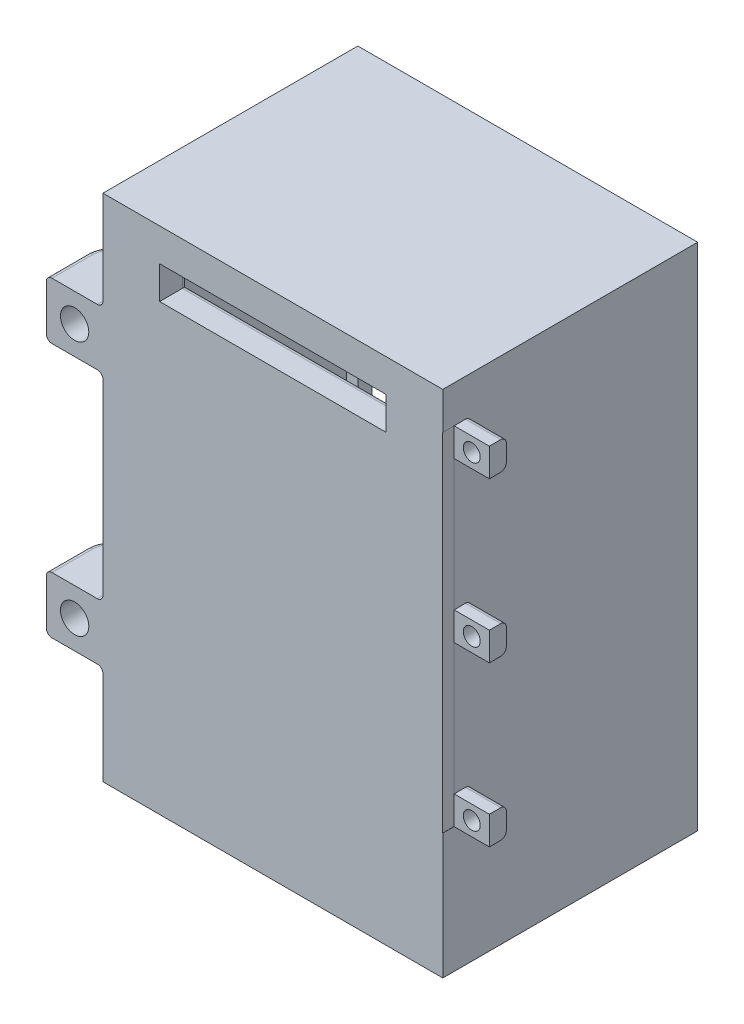
SolidWorks part; units mm, degrees
ref_plane "Plan de face" through (0, 0, 0) normal (0, 0, 1) x (1, 0, 0)
ref_plane "Plan de dessus" through (0, 0, 0) normal (0, 1, 0) x (1, 0, 0)
ref_plane "Plan de droite" through (0, 0, 0) normal (1, 0, 0) x (0, 0, -1)
sketch "Esquisse1" plane through (0, 0, 0) normal (0, 0, 1) x (1, 0, 0)
  line L0 (-42.5, 42.5) -> (0, 0)
  line L1 (-50, 50) -> (50, 50)
  line L2 (-50, 50) -> (-50, -50)
  line L3 (-50, -50) -> (50, -50)
  line L4 (50, 50) -> (50, -50)
  line L5 (-50, 50) -> (50, -50) construction
  line L6 (-50, -50) -> (50, 50) construction
  line L7 (-42.5, 42.5) -> (42.5, 42.5)
  line L8 (-42.5, 42.5) -> (-42.5, -42.5)
  line L9 (-42.5, -42.5) -> (42.5, -42.5)
  line L10 (42.5, 42.5) -> (42.5, -42.5)
  line L11 (-42.5, 42.5) -> (42.5, -42.5) construction
  line L12 (-42.5, -42.5) -> (42.5, 42.5) construction
  line L13 (0, 0) -> (42.5, -42.5)
  line L14 (-42.5, -42.5) -> (0, 0)
  line L15 (0, 0) -> (42.5, 42.5)
  line L16 (-42.5, 42.5) -> (-50, 42.5)
  line L17 (-50, 42.5) -> (-42.5, 50)
  line L18 (-42.5, 50) -> (-42.5, 42.5)
  line L19 (-46.25, 46.25) -> (-44.4822, 48.0178)
  line L20 (-46.25, 46.25) -> (-48.0178, 44.4822)
  line L21 (44.4822, -48.0178) -> (-47.9542, 44.5507)
  line L22 (44.4822, -48.0178) -> (47.9542, -44.5507)
  line L23 (-47.9542, 44.5507) -> (-44.4822, 48.0178)
  line L24 (47.9542, -44.5507) -> (-44.4822, 48.0178)
  line L25 (44.4822, -48.0178) -> (-44.4822, 48.0178) construction
  line L26 (-47.9542, 44.5507) -> (47.9542, -44.5507) construction
  line L27 (42.5, 42.5) -> (42.5, 50)
  line L28 (42.5, 42.5) -> (50, 42.5)
  line L29 (50, 42.5) -> (42.5, 50)
  line L30 (46.25, 46.25) -> (44.3148, 48.1852)
  line L31 (46.25, 46.25) -> (47.8504, 44.6496)
  line L32 (-44.3148, -48.1852) -> (48.1852, 44.3148)
  line L33 (-44.3148, -48.1852) -> (-48.1852, -44.3148)
  line L34 (48.1852, 44.3148) -> (44.3148, 48.1852)
  line L35 (-48.1852, -44.3148) -> (44.3148, 48.1852)
  line L36 (-44.3148, -48.1852) -> (44.3148, 48.1852) construction
  line L37 (48.1852, 44.3148) -> (-48.1852, -44.3148) construction
  circle A0 centre (0, 0) radius 29
  circle A1 centre (0, 0) radius 34
  point P0 (0, 0)
  point P6 (0, 0)
  dimension "D5" = 58
  dimension "D6" = 68
  dimension "D1" = 100
  dimension "D2" = 100
  dimension "D3" = 85
  dimension "D4" = 85
  dimension "D7" = 2.5
  dimension "D8" = 2.5
  dimension "D9" = 5
extrude "Boss.-Extru.2" add sketch "Esquisse1" along normal blind 10 contours L7 L35 L27 L1 L18 L24 | L33 L35 L8 L21 L16 L2 L3 L4 L28 L32 L10 L24 L22 L9 | L21 A1 L35 A0 | L32 A1 L21 A0 | L35 A1 L24 A0 | L24 A1 L32 A0 | A1 L32 L10 L15 | A1 L15 L7 L35 | L15 A1 L35 A0 | L32 A1 L15 A0 | L24 A1 L0 A0 | A1 L24 L7 L0 | L0 A1 L21 A0 | L21 A1 L13 A0 | L13 A1 L24 A0 | A1 L13 L10 L24 | A1 L21 L9 L13 | L22 L24 L10 L9 L21 | L35 L33 L32 L9 L8 | A1 L35 L8 L14 | A1 L14 L9 L32 | L35 A1 L14 A0 | L14 A1 L32 A0 | A1 L0 L8 L21 | L21 L8 L16 | L7 L24 L18 | L18 L24 L17 L20 L21 L16 | L16 L21 L17 | L21 L23 L17 L1 L2 | L24 L18 L17 | L27 L35 L29 | L35 L27 L28 L32 L29 | L32 L28 L29 | L29 L4 L1 | L10 L32 L28 | L35 L7 L27 | L16 L17 L18 region at (-31.9722, 33.7018, 0) region at (-41.3241, 43.6776, 0) region at (-33.6728, 31.9878, 0) region at (-43.6355, 41.3629, 0) region at (-44.7427, 44.7878, 0) region at (-21.3754, 23.1269, 0) region at (-23.111, 21.3913, 0) region at (-0.082, 46.3052, 0) region at (-43.8622, 0.2295, 0) region at (-47.9527, 43.1828, 0) region at (-43.1607, 48.0168, 0) region at (-0.1204, 29.0381, 0) region at (-29.033, 0.1411, 0) region at (41.2099, 43.7901, 0) region at (31.8324, 33.7334, 0) region at (-33.7334, -31.8324, 0) region at (-43.8581, -43.8581, 0) region at (-47.5002, 47.5005, 0) region at (21.2774, 23.2138, 0) region at (-23.2138, -21.2774, 0) region at (43.7901, 41.2099, 0) region at (33.7334, 31.8324, 0) region at (44.8027, 44.8027, 0) region at (43.1049, 48.1852, 0) region at (-31.8324, -33.7334, 0) region at (47.5, 47.5, 0) region at (23.2138, 21.2774, 0) region at (-21.2774, -23.2138, 0) region at (48.1852, 43.1049, 0) region at (29.033, -0.1411, 0) region at (0.1204, -29.0381, 0) region at (43.8779, -43.9513, 0) region at (33.6728, -31.9878, 0) region at (31.9722, -33.7018, 0) region at (23.111, -21.3913, 0) region at (21.3754, -23.1269, 0)
sketch "Esquisse2" plane through (0, 50, 0) normal (0, 1, 0) x (-1, 0, 0)
  line L0 (50, 5) -> (-50, 5)
  line L1 (50, 10) -> (50, 0) construction
  line L2 (-50, 10) -> (-50, 0) construction
  line L4 (2.5, 7.5) -> (-2.5, 7.5)
  line L5 (2.5, 7.5) -> (2.5, 2.5)
  line L6 (2.5, 2.5) -> (-2.5, 2.5)
  line L7 (-2.5, 7.5) -> (-2.5, 2.5)
  line L8 (2.5, 7.5) -> (-2.5, 2.5) construction
  line L9 (2.5, 2.5) -> (-2.5, 7.5) construction
  point P6 (0, 5)
  dimension "D1" = 5
  dimension "D2" = 5
extrude "Boss.-Extru.3" add sketch "Esquisse2" along normal blind 5 contours L0 L7 L6 L5 | L4 L7 L0 L5 region at (0, 50, 3.75) region at (0, 50, 6.25)
sketch "Esquisse3" plane through (0, 55, 0) normal (0, 1, 0) x (-1, 0, 0)
  line L0 (2.5, 5) -> (-2.5, 5)
  line L1 (2.5, 7.5) -> (2.5, 2.5) construction
  line L2 (-2.5, 7.5) -> (-2.5, 2.5) construction
  line L3 (2.5, 5) -> (2.5, 4)
  line L4 (2.5, 4) -> (-2.5, 4)
  line L5 (-2.5, 4) -> (-2.5, 5)
  line L6 (2.5, 5) -> (2.5, 6)
  line L7 (2.5, 6) -> (-2.5, 6)
  line L8 (-2.5, 6) -> (-2.5, 5)
  line M1 (2.5, 2.5) -> (2.5, 7.5)
  line M3 (-2.5, 7.5) -> (-2.5, 2.5)
  dimension "D1" = 1
  dimension "D2" = 1
extrude "Enlèv. mat.-Extru.1" cut sketch "Esquisse3" against normal blind 2 contours L4 L0 M1 M3 | L7 L0 M1 M3 region at (0, 55, 4.5) region at (0, 55, 5.5)
sketch "Esquisse4" plane through (-2.5, 0, 0) normal (-1, 0, 0) x (0, 0, 1)
  line L0 (6, 53) -> (6, 68)
  line L1 (6, 53) -> (4, 53)
  line L2 (4, 53) -> (4, 68)
  line L3 (4, 68) -> (6, 68)
  dimension "D1" = 15
extrude "Boss.-Extru.4" add sketch "Esquisse4" along normal blind 50 and the other way blind 55
sketch "Esquisse5" plane through (0, 0, 6) normal (0, 0, 1) x (1, 0, 0)
  line L0 (52.5, 60.5) -> (12.5, 60.5)
  line L1 (52.5, 53) -> (52.5, 68) construction
  line L2 (-52.5, 60.5) -> (-12.5, 60.5)
  line L3 (52.5, 58.5) -> (12.5, 58.5)
  line L4 (52.5, 58.5) -> (52.5, 62.5)
  line L5 (52.5, 62.5) -> (12.5, 62.5)
  line L6 (12.5, 58.5) -> (12.5, 62.5)
  line L7 (52.5, 58.5) -> (12.5, 62.5) construction
  line L8 (52.5, 62.5) -> (12.5, 58.5) construction
  line L9 (-52.5, 53) -> (-52.5, 68) construction
  line L11 (-52.5, 58.5) -> (-12.5, 58.5)
  line L12 (-52.5, 58.5) -> (-52.5, 62.5)
  line L13 (-52.5, 62.5) -> (-12.5, 62.5)
  line L14 (-12.5, 58.5) -> (-12.5, 62.5)
  line L15 (-52.5, 58.5) -> (-12.5, 62.5) construction
  line L16 (-52.5, 62.5) -> (-12.5, 58.5) construction
  point P4 (32.5, 60.5)
  point P13 (-32.5, 60.5)
  point P14 (-32.5, 60.5)
  line M8 (-52.5, 68) -> (-52.5, 53)
  dimension "D1" = 4
  dimension "D2" = 40
  dimension "D3" = 40
  dimension "D4" = 4
extrude "Enlèv. mat.-Extru.2" cut sketch "Esquisse5" against normal blind 1 contours L2 L14 L13 M8 | L11 L14 L2 M8 | L6 L0 L4 L5 | L6 L3 L4 L0 region at (32.5, 59.5, 6) region at (32.5, 61.5, 6) region at (-32.5, 61.5, 6) region at (-32.5, 59.5, 6)
sketch "Esquisse6" plane through (0, 0, 6) normal (0, 0, 1) x (1, 0, 0)
  line L0 (-52.5, 58.5) -> (-12.5, 58.5) construction
  line L1 (-12.5, 58.5) -> (-32.5, 58.5) construction
  line L2 (-32.5, 58.5) -> (-32.5, 62.5) construction
  line L3 (-52.5, 62.5) -> (-12.5, 62.5) construction
  line L4 (-32.5, 58.5) -> (-12.5, 58.5) construction
  line L5 (-12.5, 58.5) -> (-22.5, 58.5) construction
  line L6 (-22.5, 58.5) -> (-22.5, 62.5) construction
  line L7 (-52.5, 58.5) -> (-32.5, 58.5) construction
  line L8 (-42.5, 58.5) -> (-42.5, 62.5) construction
  line L9 (12.5, 58.5) -> (52.5, 58.5) construction
  line L10 (52.5, 58.5) -> (32.5, 58.5) construction
  line L11 (32.5, 58.5) -> (32.5, 62.5) construction
  line L12 (52.5, 62.5) -> (12.5, 62.5) construction
  line L13 (32.5, 58.5) -> (52.5, 58.5) construction
  line L14 (42.5, 58.5) -> (42.5, 62.5) construction
  line L15 (32.5, 58.5) -> (12.5, 58.5) construction
  line L16 (22.5, 58.5) -> (22.5, 62.5) construction
  line L18 (-44, 56.5) -> (-41, 56.5)
  line L19 (-44, 56.5) -> (-44, 64.5)
  line L20 (-44, 64.5) -> (-41, 64.5)
  line L21 (-41, 56.5) -> (-41, 64.5)
  line L22 (-44, 56.5) -> (-41, 64.5) construction
  line L23 (-44, 64.5) -> (-41, 56.5) construction
  line L24 (-24, 56.5) -> (-21, 56.5)
  line L25 (-24, 56.5) -> (-24, 64.5)
  line L26 (-24, 64.5) -> (-21, 64.5)
  line L27 (-21, 56.5) -> (-21, 64.5)
  line L28 (-24, 56.5) -> (-21, 64.5) construction
  line L29 (-24, 64.5) -> (-21, 56.5) construction
  line L30 (21, 56.5) -> (24, 56.5)
  line L31 (21, 56.5) -> (21, 64.5)
  line L32 (21, 64.5) -> (24, 64.5)
  line L33 (24, 56.5) -> (24, 64.5)
  line L34 (21, 56.5) -> (24, 64.5) construction
  line L35 (21, 64.5) -> (24, 56.5) construction
  line L36 (41, 56.5) -> (44, 56.5)
  line L37 (41, 56.5) -> (41, 64.5)
  line L38 (41, 64.5) -> (44, 64.5)
  line L39 (44, 56.5) -> (44, 64.5)
  line L40 (41, 56.5) -> (44, 64.5) construction
  line L41 (41, 64.5) -> (44, 56.5) construction
  point P24 (-42.5, 60.5)
  point P29 (-22.5, 60.5)
  point P34 (22.5, 60.5)
  point P39 (42.5, 60.5)
  dimension "D1" = 8
  dimension "D2" = 3
  dimension "D3" = 8
  dimension "D4" = 3
  dimension "D5" = 8
  dimension "D6" = 3
  dimension "D7" = 3
  dimension "D8" = 8
extrude "Boss.-Extru.5" add sketch "Esquisse6" along normal blind 2
sketch "Esquisse7" plane through (0, 0, 0) normal (0, 0, -1) x (-1, 0, 0)
  line L0 (-50, 50) -> (50, -50) construction
  line L1 (50, 50) -> (-50, -50) construction
  line L2 (-42.5, -39.0887) -> (-42.5, -42.5) construction
  line L3 (-42.5, -42.5) -> (-38.9723, -42.5) construction
  line L4 (-50, -50) -> (-42.5, -42.5) construction
  line L5 (-42.5, -42.5) -> (-50, -50) construction
  line L6 (-50, -50) -> (-46.25, -46.25) construction
  line L7 (-46.25, -46.25) -> (-46.25, 46.25) construction
  line L8 (-46.25, 46.25) -> (46.217, 46.283) construction
  line L9 (47.9517, 44.5483) -> (44.4822, 48.0178) construction
  line L10 (46.217, 46.283) -> (46.217, -46.217) construction
  line L11 (46.217, -46.217) -> (-46.25, -46.25) construction
  circle A0 centre (-46.25, 46.25) radius 2.5
  circle A1 centre (46.217, 46.283) radius 2.5
  circle A2 centre (46.217, -46.217) radius 2.5
  circle A3 centre (-46.25, -46.25) radius 2.5
  dimension "D1" = 5
  dimension "D2" = 5
  dimension "D3" = 5
  dimension "D4" = 5
extrude "Enlèv. mat.-Extru.3" cut sketch "Esquisse7" against normal blind 10
fillet "Congé1" radius 5 2 edges at (0, 55, 7.5) (0, 55, 2.5)
fillet "Congé4" radius 1 6 edges at (-27.5, 53, 6) (27.5, 53, 6) (27.5, 53, 4) (-27.5, 53, 4) (0, 68, 6) (0, 68, 4)
fillet "Congé5" radius 1 8 edges at (50, 0, 10) (0, -50, 10) (-50, 0, 10) (0, 50, 10) (0, -50, 0) (-50, 0, 0) (0, 50, 0) (50, 0, 0)
fillet "Congé6" radius 1 28 edges at (-49.7071, -49.7071, 9.7071) (-49.7071, -49.7071, 0.2929) (49.7071, -49.7071, 9.7071) (49.7071, -49.7071, 0.2929) (-49.7071, 49.7071, 9.7071) (-49.7071, 49.7071, 0.2929) (49.7071, 49.7071, 9.7071) (49.7071, 49.7071, 0.2929) (-42.5, 0.2295, 0) (-34.1994, -30.3291, 0) (-30.3291, -34.1994, 0) (0.1713, -42.5, 0) (30.5991, -34.1148, 0) (34.0989, -30.6756, 0) (42.5, -0.2295, 0) (34.1994, 30.3291, 0) (30.3291, 34.1994, 0) (-0.1713, 42.5, 0) (-30.5991, 34.1148, 0) (-34.0989, 30.6756, 0) (-33.9997, 0.1543, 0) (-0.13, 33.9998, 0) (33.9997, -0.1543, 0) (0.13, -33.9998, 0) (-50, -50, 5) (50, -50, 5) (-50, 50, 5) (50, 50, 5)
fillet "Congé7" radius 2 8 edges at (42.5, 56.5, 8) (42.5, 64.5, 8) (22.5, 56.5, 8) (22.5, 64.5, 8) (-22.5, 56.5, 8) (-22.5, 64.5, 8) (-42.5, 56.5, 8) (-42.5, 64.5, 8)
sketch "Esquisse8" plane through (0, 50, 0) normal (0, 1, 0) x (-1, 0, 0)
  line L0 (49, 5) -> (-49, 5) construction
  line L1 (49, 1) -> (49, 9) construction
  line L2 (-49, 9) -> (-49, 1) construction
  line L3 (-49, 5) -> (0, 5) construction
  line L4 (0, 5) -> (-24.5, 5) construction
  line L5 (-24.5, 5) -> (-49, 5) construction
  line L6 (-49, 5) -> (-36.75, 5) construction
  line L7 (-36.75, 5) -> (-36.75, 9) construction
  line L8 (49, 9) -> (-49, 9) construction
  line L9 (-36.75, 9) -> (-36.75, 1) construction
  line L10 (-49, 1) -> (49, 1) construction
  line L11 (49, 5) -> (0, 5) construction
  line L12 (0, 5) -> (24.5, 5) construction
  line L13 (24.5, 5) -> (49, 5) construction
  line L14 (49, 5) -> (36.75, 5) construction
  line L15 (36.75, 1) -> (36.75, 9) construction
  line L17 (39.25, 2.5) -> (34.25, 2.5)
  line L18 (39.25, 2.5) -> (39.25, 7.5)
  line L19 (39.25, 7.5) -> (34.25, 7.5)
  line L20 (34.25, 2.5) -> (34.25, 7.5)
  line L21 (39.25, 2.5) -> (34.25, 7.5) construction
  line L22 (39.25, 7.5) -> (34.25, 2.5) construction
  line L23 (-34.25, 2.5) -> (-39.25, 2.5)
  line L24 (-34.25, 2.5) -> (-34.25, 7.5)
  line L25 (-34.25, 7.5) -> (-39.25, 7.5)
  line L26 (-39.25, 2.5) -> (-39.25, 7.5)
  line L27 (-34.25, 2.5) -> (-39.25, 7.5) construction
  line L28 (-34.25, 7.5) -> (-39.25, 2.5) construction
  dimension "D1" = 5
  dimension "D2" = 5
  dimension "D3" = 5
  dimension "D4" = 5
extrude "Boss.-Extru.6" add sketch "Esquisse8" along normal blind 5
fillet "Congé8" radius 5 4 edges at (-36.75, 55, 7.5) (36.75, 55, 7.5) (-36.75, 55, 2.5) (36.75, 55, 2.5)
sketch "Esquisse9" plane through (0, 0, 10) normal (0, 0, 1) x (1, 0, 0)
  line L0 (-46.217, -46.217) -> (0, -46.217) construction
  line L1 (0, -46.217) -> (-105.737, -46.217) construction
  line L2 (0, 0) -> (-223.2664, 0) construction
  line L3 (0, -46.217) -> (0, 0) construction
  line L4 (0, 0) -> (0, 46.5692) construction
  line L5 (0, 46.5692) -> (-46.217, 46.283) construction
  line L6 (-179.1375, 46.283) -> (-46.217, 46.283) construction
  line L7 (-46.217, 46.283) -> (-46.217, -46.217) construction
  line L8 (-46.217, 46.283) -> (-56.217, 46.283) construction
  line L9 (-56.217, 46.283) -> (-56.217, 0) construction
  line L10 (-56.217, 0) -> (-46.217, 0) construction
  line L11 (-56.217, 46.283) -> (-56.217, 23.1415) construction
  line L12 (-56.217, 23.1415) -> (-56.217, 46.283) construction
  line L13 (-56.217, 46.283) -> (-56.217, 34.7123) construction
  line L14 (-56.217, 34.7123) -> (-46.217, 34.7123) construction
  line L15 (-46.217, 34.7123) -> (-46.217, 0) construction
  line L16 (-46.217, 0) -> (-56.217, 0) construction
  line L17 (-56.217, 0) -> (-56.217, 23.1415) construction
  line L18 (-56.217, 23.1415) -> (-56.217, 11.5708) construction
  line L19 (-56.217, 11.5708) -> (-46.217, 11.5708) construction
  line L20 (-56.217, 6.5708) -> (-56.217, -16.5712) construction
  line L21 (-46.217, 11.5708) -> (-56.217, 11.5708)
  line L22 (-46.217, 11.5708) -> (-46.217, 6.5708)
  line L23 (-46.217, 6.5708) -> (-56.217, 6.5708)
  line L24 (-56.217, 11.5708) -> (-56.217, 6.5708)
  line L25 (-46.217, 34.7123) -> (-56.217, 34.7123)
  line L26 (-46.217, 34.7123) -> (-46.217, 39.7123)
  line L27 (-46.217, 39.7123) -> (-56.217, 39.7123)
  line L28 (-56.217, 34.7123) -> (-56.217, 39.7123)
  line L29 (-56.217, 46.283) -> (-116.217, 46.283)
  line L30 (-56.217, 46.283) -> (-56.217, -43.717)
  line L31 (-56.217, -43.717) -> (-116.217, -43.717)
  line L32 (-116.217, 46.283) -> (-116.217, -43.717)
  line L34 (-56.217, -16.5712) -> (-46.217, -16.5712)
  line L35 (-56.217, -16.5712) -> (-56.217, -21.5712)
  line L36 (-56.217, -21.5712) -> (-46.217, -21.5712)
  line L37 (-46.217, -16.5712) -> (-46.217, -21.5712)
  line M4 (-49, 49) -> (-49, -49)
  dimension "D1" = 10
  dimension "D2" = 5
  dimension "D3" = 5
  dimension "D4" = 90
  dimension "D5" = 60
  dimension "D6" = 23.142
  dimension "D7" = 5
extrude "Boss.-Extru.7" add sketch "Esquisse9" against normal blind 5 contours L29 L32 L31 L30 L24 L28 | L30 L36 L34 M4 | L37 L34 L36 M4 | L21 L24 L23 M4 | L23 L22 L21 M4 | L28 L25 L27 M4 | L26 L27 L25 M4 region at (-47.6085, 9.0708, 10) region at (-52.6085, 9.0708, 10) region at (-86.217, 1.283, 10) region at (-47.6085, 37.2123, 10) region at (-52.6085, 37.2123, 10) region at (-52.6085, -19.0712, 10) region at (-47.6085, -19.0712, 10)
sketch "Esquisse10" plane through (0, 0, 5) normal (0, 0, -1) x (-1, 0, 0)
  line L0 (116.217, 1.283) -> (113.717, 1.283) construction
  line L1 (116.217, -43.717) -> (56.217, -43.717) construction
  line L2 (58.717, 6.3504) -> (58.717, 43.783)
  line L3 (58.717, 43.783) -> (86.217, 43.783)
  line L4 (86.217, 43.783) -> (113.717, 43.783)
  line L5 (116.217, 46.283) -> (116.217, -43.717) construction
  line L6 (116.217, 1.283) -> (56.217, 6.5708) construction
  line L7 (56.217, 6.5708) -> (58.717, 6.3504) construction
  line L8 (86.217, 6.283) -> (86.217, 46.283) construction
  line L9 (56.217, 46.283) -> (116.217, 46.283) construction
  line L10 (86.217, 46.283) -> (86.217, -43.717) construction
  line L11 (86.217, -43.717) -> (86.217, -41.217) construction
  line L12 (86.217, 46.283) -> (86.217, 43.783) construction
  line L13 (116.217, 1.283) -> (113.717, 1.283) construction
  line L14 (113.717, 43.783) -> (113.717, 1.283)
  line L15 (113.717, 1.283) -> (113.717, -41.217)
  line L16 (113.717, -41.217) -> (86.217, -41.217)
  line L17 (86.217, -41.217) -> (58.717, -41.217)
  line L18 (58.717, -41.217) -> (58.717, 6.3504)
  line L20 (56.217, 46.283) -> (116.217, 46.283)
  line L21 (56.217, 46.283) -> (56.217, -43.717)
  line L22 (56.217, -43.717) -> (116.217, -43.717)
  line L23 (116.217, 46.283) -> (116.217, -43.717)
  dimension "D1" = 2.5
  dimension "D2" = 2.5
  dimension "D3" = 2.5
  dimension "D4" = 2.5
extrude "Boss.-Extru.8" add sketch "Esquisse10" along normal blind 40
sketch "Esquisse13" plane through (0, 0, 5) normal (0, 0, -1) x (-1, 0, 0)
  circle A0 centre (77.258, 24.183) radius 1.4
  circle A1 centre (105.208, 24.183) radius 1.4
  circle A2 centre (62.108, -26.617) radius 1.4
  dimension "D1" = 2.8
  dimension "D2" = 2.8
  dimension "D3" = 2.8
extrude "Boss.-Extru.10" add sketch "Esquisse13" along normal blind 5
sketch "Esquisse14" plane through (0, 0, 5) normal (0, 0, -1) x (-1, 0, 0)
  circle A0 centre (110.408, -28.017) radius 1.4
  dimension "D1" = 2.8
extrude "Boss.-Extru.11" add sketch "Esquisse14" along normal blind 5
sketch "Esquisse15" plane through (0, -43.717, 0) normal (0, -1, 0) x (1, 0, 0)
  line L0 (-104.1082, 4.35) -> (-104.1082, 3.35) construction
  line L1 (-100.408, -7.45) -> (-109.108, -7.45)
  line L2 (-100.408, -7.45) -> (-100.408, 3.35)
  line L3 (-100.408, 3.35) -> (-109.108, 3.35)
  line L4 (-109.108, -7.45) -> (-109.108, 3.35)
  line L5 (-99.408, -8.45) -> (-110.108, -8.45)
  line L6 (-99.408, -8.45) -> (-99.408, 4.35)
  line L7 (-99.408, 4.35) -> (-110.108, 4.35)
  line L8 (-110.108, -8.45) -> (-110.108, 4.35)
  line L9 (-104.1082, 3.35) -> (-104.1082, -7.45) construction
  line L10 (-104.1082, -7.45) -> (-104.1082, -8.45) construction
  line L11 (-99.408, -0.9666) -> (-100.408, -0.9666) construction
  line L12 (-100.408, -0.9666) -> (-109.108, -0.9666) construction
  line L13 (-109.108, -0.9666) -> (-110.108, -0.9666) construction
  line L15 (-100.408, -7.45) -> (-109.108, -7.45)
  line L16 (-100.408, -7.45) -> (-100.408, 3.35)
  line L17 (-100.408, 3.35) -> (-109.108, 3.35)
  line L18 (-109.108, -7.45) -> (-109.108, 3.35)
  dimension "D1" = 1
  dimension "D2" = 1
  dimension "D3" = 1
  dimension "D4" = 1
extrude "Enlèv. mat.-Extru.5" cut sketch "Esquisse15" against normal blind 5 contours L4 L1 L2 L3 | L8 L5 L6 L7 L1 L4 L3 L2 region at (-104.758, -43.717, -2.05) region at (-104.758, -43.717, -8.2832)
sketch "Esquisse16" plane through (0, -43.717, 0) normal (0, -1, 0) x (1, 0, 0)
  line L0 (-74.708, 3.45) -> (-74.708, 4.45) construction
  line L1 (-80.658, 3.45) -> (-68.758, 3.45)
  line L2 (-80.658, 3.45) -> (-80.658, -7.15)
  line L3 (-80.658, -7.15) -> (-68.758, -7.15)
  line L4 (-68.758, 3.45) -> (-68.758, -7.15)
  line L5 (-74.708, 4.45) -> (-74.708, -7.15) construction
  line L6 (-74.708, -7.15) -> (-74.708, -8.15) construction
  line L7 (-80.658, -1.85) -> (-74.708, -1.85) construction
  line L8 (-74.708, -1.85) -> (-68.758, -1.85) construction
  line L9 (-68.758, -1.85) -> (-67.758, -1.85) construction
  line L10 (-67.758, -1.85) -> (-80.658, -1.85) construction
  line L11 (-80.658, -1.85) -> (-81.658, -1.85) construction
  line L12 (-81.658, -1.85) -> (-81.658, 4.45) construction
  line L13 (-81.658, 4.45) -> (-74.708, 4.45) construction
  line L14 (-74.708, 4.45) -> (-67.758, 4.45) construction
  line L15 (-67.758, 4.45) -> (-67.758, -1.85) construction
  line L16 (-67.758, -1.85) -> (-67.758, -8.15) construction
  line L17 (-67.758, -8.15) -> (-74.708, -8.15) construction
  line L18 (-74.708, -8.15) -> (-81.658, -8.15) construction
  line L19 (-81.658, -8.15) -> (-81.658, -1.85) construction
  line L21 (-81.658, 4.45) -> (-67.758, 4.45)
  line L22 (-81.658, 4.45) -> (-81.658, -8.15)
  line L23 (-81.658, -8.15) -> (-67.758, -8.15)
  line L24 (-67.758, 4.45) -> (-67.758, -8.15)
  line L25 (-80.658, 3.45) -> (-68.758, 3.45)
  line L26 (-80.658, 3.45) -> (-80.658, -7.15)
  line L27 (-80.658, -7.15) -> (-68.758, -7.15)
  line L28 (-68.758, 3.45) -> (-68.758, -7.15)
  dimension "D1" = 1
  dimension "D2" = 1
  dimension "D3" = 1
  dimension "D4" = 1
extrude "Enlèv. mat.-Extru.6" cut sketch "Esquisse16" against normal blind 5 contours L4 L1 L2 L3 | L24 L21 L22 L23 L1 L4 L3 L2 region at (-74.708, -43.717, -1.85) region at (-74.708, -43.717, 4.2624)
sketch "Esquisse17" plane through (0, 0, 5) normal (0, 0, -1) x (-1, 0, 0)
  line L0 (116.217, 46.283) -> (56.217, 46.283) construction
  line L1 (56.217, 46.283) -> (116.217, 46.283) construction
  line L2 (56.217, 46.283) -> (56.217, 39.7123) construction
  line L3 (56.217, 46.283) -> (56.217, 34.7123) construction
  line L4 (56.217, 34.7123) -> (116.217, 34.7123) construction
  line L5 (116.217, 46.283) -> (116.217, -43.717) construction
  line L6 (116.217, 34.7123) -> (116.217, 46.283) construction
  line L7 (116.217, 46.283) -> (116.217, 1.283) construction
  line L8 (116.217, 1.283) -> (56.217, 1.283) construction
  line L9 (56.217, 6.5708) -> (56.217, -16.5712) construction
  line L10 (56.217, 1.283) -> (56.217, 34.7123) construction
  line L11 (56.217, 34.7123) -> (116.217, 1.283) construction
  line L12 (116.217, 1.283) -> (116.217, 34.7123) construction
  line L13 (116.217, 34.7123) -> (56.217, 1.283) construction
  line L14 (116.217, 34.7123) -> (116.217, 40.4976) construction
  line L15 (116.217, 40.4976) -> (56.217, 40.4976) construction
  line L16 (56.217, 40.4976) -> (56.217, 34.7123) construction
  line L17 (116.217, 40.4976) -> (106.217, 40.4976) construction
  line L18 (106.217, 40.4976) -> (106.217, 34.7123) construction
  line L19 (56.217, 40.4976) -> (66.217, 40.4976) construction
  line L20 (66.217, 40.4976) -> (66.217, 34.7123) construction
  line L22 (106.217, 40.4976) -> (66.217, 40.4976)
  line L23 (106.217, 40.4976) -> (106.217, 34.7123)
  line L24 (106.217, 34.7123) -> (66.217, 34.7123)
  line L25 (66.217, 40.4976) -> (66.217, 34.7123)
  dimension "D1" = 10
  dimension "D2" = 10
extrude "Enlèv. mat.-Extru.7" cut sketch "Esquisse17" against normal blind 5
sketch "Esquisse18" plane through (-116.217, 0, 0) normal (-1, 0, 0) x (0, 0, 1)
  line L0 (10, 46.283) -> (10, -43.717) construction
  line L1 (10, -43.717) -> (-35, -43.717) construction
  line L2 (-35, -43.717) -> (-35, 46.283) construction
  line L3 (-35, 46.283) -> (10, 46.283) construction
  line L4 (10, 46.283) -> (10, 1.283) construction
  line L5 (10, 1.283) -> (-35, 1.283) construction
  line L6 (-35, 1.283) -> (10, 1.283) construction
  line L7 (10, 1.283) -> (10, -43.717) construction
  line L8 (10, -43.717) -> (10, -21.217) construction
  line L9 (10, -21.217) -> (-35, -21.217) construction
  line L10 (-35, -21.217) -> (-35, 46.283) construction
  line L11 (-35, 46.283) -> (10, 46.283) construction
  line L12 (10, 46.283) -> (10, 1.283) construction
  line L13 (10, 1.283) -> (10, 23.783) construction
  line L14 (10, 23.783) -> (-35, 23.783) construction
  line L15 (-35, 23.783) -> (-12.5, 23.783) construction
  line L16 (-12.5, 23.783) -> (-12.5, 1.283) construction
  line L17 (-12.5, 1.283) -> (-12.5, -21.217) construction
  line L18 (-12.5, 23.783) -> (10, 23.783) construction
  line L19 (10, 23.783) -> (-1.25, 23.783) construction
  line L20 (-1.25, 23.783) -> (-1.25, -21.217) construction
  line L21 (-1.25, -21.217) -> (-12.5, -21.217) construction
  line L22 (-1.25, 23.783) -> (-1.25, 46.283) construction
  line L23 (-1.25, 46.283) -> (-1.25, -21.217) construction
  line L24 (-1.25, -21.217) -> (-1.25, -43.717) construction
  line L26 (-1.25, -26.217) -> (10, -26.217)
  line L27 (-1.25, -26.217) -> (-1.25, -16.217)
  line L28 (-1.25, -16.217) -> (10, -16.217)
  line L29 (10, -26.217) -> (10, -16.217)
  line L30 (-1.25, 18.783) -> (10, 18.783)
  line L31 (-1.25, 18.783) -> (-1.25, 28.783)
  line L32 (-1.25, 28.783) -> (10, 28.783)
  line L33 (10, 18.783) -> (10, 28.783)
  dimension "D1" = 10
  dimension "D2" = 5
  dimension "D3" = 5
  dimension "D4" = 10
extrude "Boss.-Extru.12" add sketch "Esquisse18" along normal blind 10
sketch "Esquisse19" plane through (0, 0, -1.25) normal (0, 0, -1) x (-1, 0, 0)
  line L0 (116.217, 28.783) -> (126.217, 18.783) construction
  line L1 (126.217, 18.783) -> (126.217, 28.783) construction
  line L2 (126.217, 28.783) -> (116.217, 28.783) construction
  line L3 (126.217, 28.783) -> (126.217, 18.783) construction
  line L4 (126.217, 28.783) -> (121.217, 23.783) construction
  line L5 (121.217, 23.783) -> (121.217, -26.217) construction
  line L6 (126.217, -26.217) -> (116.217, -26.217) construction
  line L7 (116.217, -26.217) -> (121.217, -26.217) construction
  line L8 (126.217, -16.217) -> (116.217, -26.217) construction
  line L9 (121.217, -26.217) -> (126.217, -26.217) construction
  line L10 (126.217, -26.217) -> (116.217, -16.217) construction
  line L11 (116.217, -16.217) -> (121.217, -21.217) construction
  circle A0 centre (121.217, -21.217) radius 2.5
  circle A1 centre (121.217, 23.783) radius 2.5
  dimension "D1" = 5
  dimension "D2" = 5
extrude "Enlèv. mat.-Extru.9" cut sketch "Esquisse19" against normal through all
fillet "Congé10" radius 1 4 edges at (-106.217, 37.6049, 5) (-86.217, 34.7123, 5) (-66.217, 37.6049, 5) (-86.217, 40.4976, 5)
fillet "Congé11" radius 1 1 edges at (-53.1085, -21.5712, 5)
fillet "Congé12" radius 1 5 edges at (-53.1085, 39.7123, 5) (-53.1085, 34.7123, 5) (-53.1085, 11.5708, 5) (-53.1085, 6.5708, 5) (-53.1085, -16.5712, 5)
fillet "Congé13" radius 4 2 edges at (-126.217, 23.783, -1.25) (-126.217, -21.217, -1.25)
fillet "Congé14" radius 1 18 edges at (-116.217, 28.783, 4.375) (-116.217, -21.217, -1.25) (-126.217, 28.783, 6.375) (-125.0454, 28.783, -0.0784) (-119.217, 28.783, -1.25) (-116.217, 23.783, -1.25) (-116.217, 18.783, 4.375) (-126.217, 18.783, 6.375) (-125.0454, 18.783, -0.0784) (-119.217, 18.783, -1.25) (-119.217, -16.217, -1.25) (-125.0454, -16.217, -0.0784) (-126.217, -16.217, 6.375) (-126.217, -26.217, 6.375) (-125.0454, -26.217, -0.0784) (-119.217, -26.217, -1.25)
sketch "Esquisse20" plane through (-116.217, 0, 0) normal (-1, 0, 0) x (0, 0, 1)
  line L1 (-35, 46.283) -> (10, 46.283) construction
  line L2 (-32.5, 46.283) -> (-32.5, 44.783) construction
  line L3 (-35, -43.717) -> (-32.5, -43.717) construction
  line L4 (-35, -43.717) -> (10, -43.717) construction
  line L5 (-32.5, -43.717) -> (-32.5, -42.217) construction
  line L7 (-32.5, -42.217) -> (-30.5, -42.217)
  line L8 (-32.5, -42.217) -> (-32.5, 44.783)
  line L9 (-32.5, 44.783) -> (-30.5, 44.783)
  line L10 (-30.5, -42.217) -> (-30.5, 44.783)
  dimension "D1" = 1.5
  dimension "D2" = 2
  dimension "D3" = 1.5
  dimension "D4" = 2.5
extrude "Enlèv. mat.-Extru.10" cut sketch "Esquisse20" against normal blind 58.5
sketch "Esquisse21" plane through (50, 0, 0) normal (1, 0, 0) x (0, 0, -1)
  line L0 (-9, 49) -> (-9, -49) construction
  line L1 (-9, 44.2245) -> (-1, 44.2245)
  line L2 (-9, 44.2245) -> (-9, 36.5324)
  line L3 (-9, 36.5324) -> (-1, 36.5324)
  line L4 (-1, 44.2245) -> (-1, 36.5324)
  line L5 (-1, -49) -> (-1, 49) construction
  line L7 (-9, -34.3741) -> (-1, -34.3741)
  line L8 (-9, -34.3741) -> (-9, -41.3595)
  line L9 (-9, -41.3595) -> (-1, -41.3595)
  line L10 (-1, -34.3741) -> (-1, -41.3595)
extrude "Boss.-Extru.17" add sketch "Esquisse21" along normal blind 10
sketch "Esquisse29" plane through (60, 0, 0) normal (1, 0, 0) x (0, 0, -1)
  line L1 (-9, 49.4493) -> (36.0244, 49.4493)
  line L2 (-9, 49.4493) -> (-9, -48.2057)
  line L3 (-9, -48.2057) -> (36.0244, -48.2057)
  line L4 (36.0244, 49.4493) -> (36.0244, -48.2057)
extrude "Boss.-Extru.19" [suppressed] add sketch "Esquisse29" along normal blind 100
sketch "Esquisse30" [suppressed] plane through (0, 0, -36.0244) normal (0, 0, -1) x (-1, 0, 0)
  line L1 (-156.3216, 44.7075) -> (-64.9621, 44.7075)
  line L2 (-156.3216, 44.7075) -> (-156.3216, -43.3176)
  line L3 (-156.3216, -43.3176) -> (-64.9621, -43.3176)
  line L4 (-64.9621, 44.7075) -> (-64.9621, -43.3176)
extrude "Enlèv. mat.-Extru.12" [suppressed] cut sketch "Esquisse30" against normal blind 37
sketch "Esquisse31" [suppressed] plane through (0, -48.2057, 0) normal (0, -1, 0) x (1, 0, 0)
  line L0 (160, -36.0244) -> (60, 9) construction
  line L1 (60, 9) -> (60, -36.0244) construction
  line L2 (60, -36.0244) -> (160, 9) construction
  line L3 (110, -13.5122) -> (60, 9) construction
  line L4 (110, -13.5122) -> (110, 9) construction
  line L5 (160, 9) -> (60, 9) construction
  line L6 (110, 9) -> (110, -13.5122) construction
  line L7 (110, -13.5122) -> (60, -13.5122) construction
  line L8 (60, -13.5122) -> (110, 9) construction
  line L9 (110, 9) -> (85, -2.2561) construction
  line L11 (96.9434, -7.6335) -> (73.0566, -7.6335)
  line L12 (96.9434, -7.6335) -> (96.9434, 3.1214)
  line L13 (96.9434, 3.1214) -> (73.0566, 3.1214)
  line L14 (73.0566, -7.6335) -> (73.0566, 3.1214)
  line L15 (96.9434, -7.6335) -> (73.0566, 3.1214) construction
  line L16 (96.9434, 3.1214) -> (73.0566, -7.6335) construction
extrude "Enlèv. mat.-Extru.13" [suppressed] cut sketch "Esquisse31" against normal blind 10
fillet "Congé15" [suppressed] radius 10
sketch "Esquisse36" plane through (-50, 0, 0) normal (-1, 0, 0) x (0, 0, 1)
  line L0 (9, -50) -> (1, -50) construction
  line L1 (-4, -49) -> (21, -49)
  line L2 (-4, -49) -> (-4, 101)
  line L3 (-4, 101) -> (21, 101)
  line L4 (21, -49) -> (21, 101)
  dimension "D1" = 25
  dimension "D2" = 5
  dimension "D3" = 150
  dimension "D4" = 1
extrude "Enlèv. mat.-Extru.17" cut sketch "Esquisse36" against normal blind 110
sketch "Esquisse37" plane through (-50, 0, 0) normal (1, 0, 0) x (0, 0, -1)
  line L0 (-6, -21.5712) -> (-10, -21.5712) construction
  line L1 (-10, 39.7123) -> (-8, 39.7123)
  line L2 (-10, 39.7123) -> (-10, -21.5712)
  line L3 (-10, -21.5712) -> (-8, -21.5712)
  line L4 (-8, 39.7123) -> (-8, -21.5712)
extrude "Enlèv. mat.-Extru.18" cut sketch "Esquisse37" against normal blind 6.25
sketch "Esquisse38" plane through (0, 0, 8) normal (0, 0, 1) x (1, 0, 0)
  line L0 (-53.1085, 39.7123) -> (-53.1085, 34.7123) construction
  line L1 (-56.217, 39.7123) -> (-50, 39.7123) construction
  line L2 (-50, 34.7123) -> (-56.217, 34.7123) construction
  line L3 (-53.1085, 34.7123) -> (-53.1085, 37.2123) construction
  line L4 (-53.1085, 37.2123) -> (-53.1085, 11.5708) construction
  line L5 (-50, 11.5708) -> (-56.217, 11.5708) construction
  line L6 (-53.1085, 11.5708) -> (-53.1085, 6.5708) construction
  line L7 (-50, 6.5708) -> (-56.217, 6.5708) construction
  line L8 (-53.1085, 6.5708) -> (-53.1085, 9.0708) construction
  line L9 (-53.1085, 9.0708) -> (-53.1085, -16.5712) construction
  line L10 (-56.217, -16.5712) -> (-50, -16.5712) construction
  line L11 (-53.1085, -16.5712) -> (-53.1085, -21.5712) construction
  line L12 (-56.217, -21.5712) -> (-50, -21.5712) construction
  line L13 (-53.1085, -21.5712) -> (-53.1085, -19.0712) construction
  circle A0 centre (-53.1085, 37.2123) radius 1.5
  circle A1 centre (-53.1085, 9.0708) radius 1.5
  circle A2 centre (-53.1085, -19.0712) radius 1.5
  dimension "D1" = 3
  dimension "D2" = 3
  dimension "D3" = 3
extrude "Enlèv. mat.-Extru.19" cut sketch "Esquisse38" against normal blind 6.25
